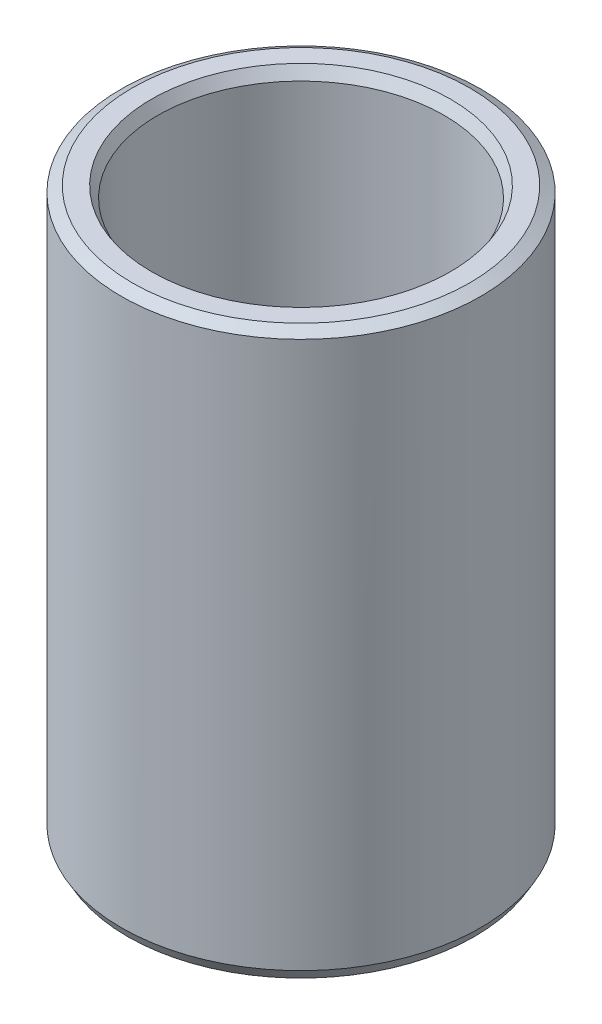
SolidWorks part; units mm, degrees
ref_plane "Front Plane" through (0, 0, 0) normal (0, 0, 1) x (1, 0, 0)
ref_plane "Top Plane" through (0, 0, 0) normal (0, 1, 0) x (1, 0, 0)
ref_plane "Right Plane" through (0, 0, 0) normal (1, 0, 0) x (0, 0, -1)
sketch "Sketch1" plane through (0, 0, 0) normal (0, 1, 0) x (1, 0, 0)
  circle A0 centre (0, 0) radius 25
  dimension "SLEEVE_OD" = 50
extrude "Boss-Extrude1" add sketch "Sketch1" along normal blind 78.4504
sketch "Sketch2" plane through (0, 0, 0) normal (0, 1, 0) x (1, 0, 0)
  circle A0 centre (0, 0) radius 19.9224
  dimension "BORE_D" = 39.8447
extrude "Cut-Extrude1" cut sketch "Sketch2" along normal through all
chamfer "Chamfer1" distance 0.875 angle 60 4 edges at (0, 78.4504, 19.9224) (0, 0, 19.9224) (0, 0, 25) (0, 78.4504, 25) first distance on face at (0, 78.4504, 19.9224) first distance on face at (0, 0, 19.9224) first distance on face at (0, 78.4504, 25)
